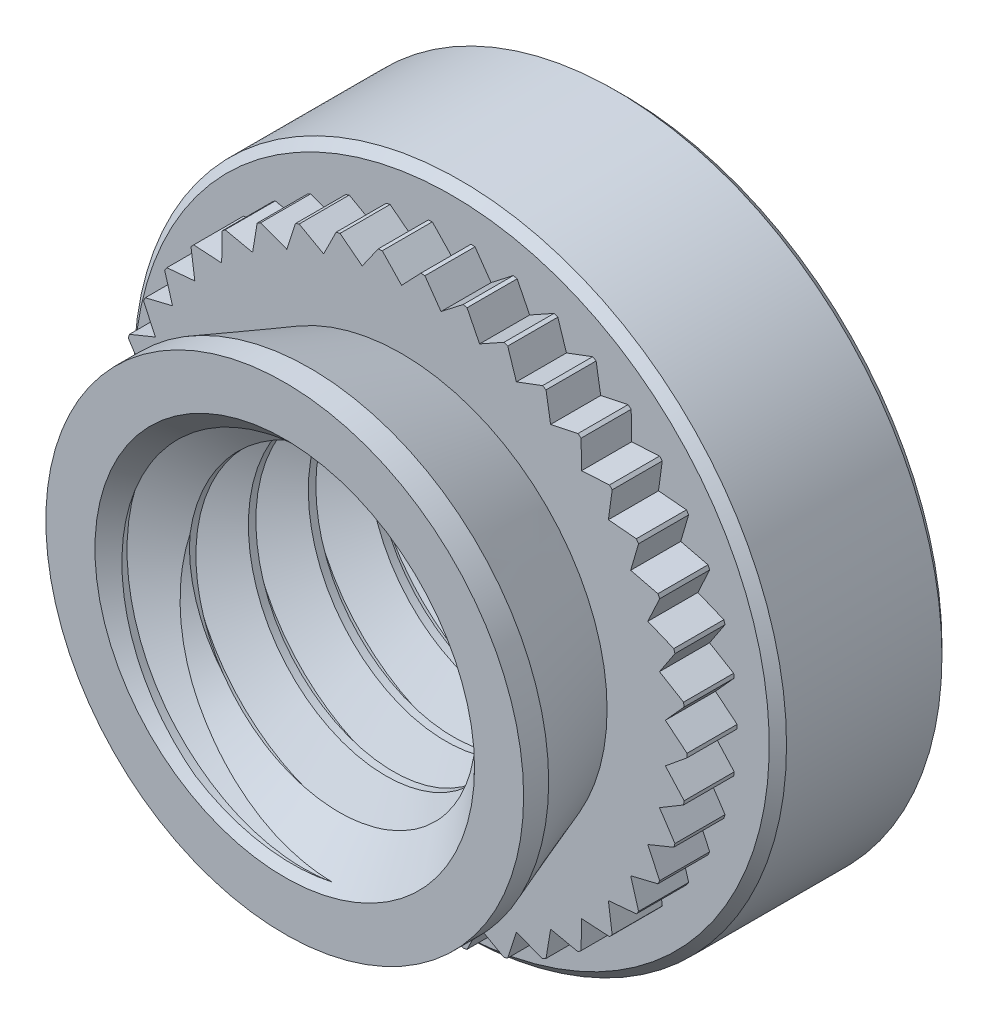
SolidWorks part; units mm, degrees
ref_plane "Front Plane" through (0, 0, 0) normal (0, 0, 1) x (1, 0, 0)
ref_plane "Top Plane" through (0, 0, 0) normal (0, 1, 0) x (1, 0, 0)
ref_plane "Right Plane" through (0, 0, 0) normal (1, 0, 0) x (0, 0, -1)
sketch "Sketch1" plane through (0, 0, 0) normal (0, 0, 1) x (1, 0, 0)
  line L0 (0, 0) -> (1.2065, -2.0897) construction
  line L1 (0, 0) -> (0, -2.413) construction
  circle A0 centre (0, 0) radius 4.318 construction
  circle A1 centre (0, 0) radius 3.1623 construction
  circle A2 centre (0, 0) radius 2.413 construction
  point P8 (1.2065, -2.0897)
  dimension "Head OD" = 8.636
  dimension "Shank OD" = 6.3246
  dimension "Thread ID" = 4.826
  dimension "D1" = 30
sketch "Sketch2" plane through (0, 0, 0) normal (1, 0, 0) x (0, 0, -1)
  line L0 (2.2479, 4.318) -> (-0.0381, 4.318) construction
  line L1 (-0.0381, 4.318) -> (-0.0381, -4.318) construction
  line L2 (-0.0381, -4.318) -> (2.2479, -4.318) construction
  line L3 (2.2479, -4.318) -> (2.2479, 4.318) construction
  line L4 (-0.0381, 3.7783) -> (-0.701, 3.7783) construction
  line L5 (-0.701, 3.7783) -> (-0.701, -3.7783) construction
  line L6 (-0.701, -3.7783) -> (-0.0381, -3.7783) construction
  line L7 (-2.2479, 3.1623) -> (-1.9164, 3.1623) construction
  line L8 (-2.2479, 3.1623) -> (-2.2479, -3.1623) construction
  line L9 (-2.2479, -3.1623) -> (-1.9164, -3.1623) construction
  line L10 (-2.2479, 0) -> (2.2479, 0) construction
  line L11 (-1.9164, -3.1623) -> (-0.701, -2.7199) construction
  line L12 (-1.9164, 3.1623) -> (-0.701, 2.7199) construction
  line L13 (0, -3.1623) -> (-2.2479, -3.1623) construction
  line L16 (2.2479, 2.413) -> (-2.2479, 2.413) construction
  line L19 (2.1983, 2.4989) -> (2.992, 2.4989) construction
  line L20 (2.992, 2.4989) -> (2.5952, 1.8115) construction
  line L21 (2.5952, 1.8115) -> (2.1983, 2.4989) construction
  line L22 (2.2231, 2.456) -> (2.9672, 2.456) construction
  line L23 (2.2479, 2.413) -> (2.9424, 2.413) construction
  line L24 (2.5456, 1.8974) -> (2.6448, 1.8974) construction
  line L25 (2.5952, 1.8974) -> (2.5952, 1.8115) construction
  line L26 (2.5952, 2.413) -> (2.5952, 2.4989) construction
  point P14 (-0.701, 0)
  point P15 (0, -4.318)
  point P16 (0, 2.413)
  point P37 (2.5952, 2.456)
  point P41 (0, 0)
  dimension "Head Height" = 2.286
  dimension "Shank Ht." = 2.2098
  dimension "D1" = 0.6629
  dimension "D3" = 7.5565
  dimension "Pitch" = 0.7937
  dimension "D7" = 0.0992
  dimension "D2" = 0.6159
  dimension "Total Height" = 4.4958
  dimension "D4" = 20
  dimension "D5" = 0.3315
sketch "Sketch3" plane through (0, 0, 0) normal (1, 0, 0) x (0, 0, -1)
  line L0 (-2.2479, 2.413) -> (2.2479, 2.413)
  line L1 (2.2479, 2.413) -> (2.2479, 4.318)
  line L2 (2.2479, 4.318) -> (-0.0381, 4.318)
  line L3 (-0.0381, 4.318) -> (-0.0381, 3.7783)
  line L4 (-0.0381, 3.7783) -> (-0.701, 3.7783)
  line L5 (-0.701, 3.7783) -> (-0.701, 2.7199)
  line L7 (-2.2479, 3.1623) -> (-2.2479, 2.413)
  line L8 (-2.2479, 0) -> (2.2479, 0) construction
  line L9 (-2.2479, 3.1623) -> (-1.9164, 3.1623)
  line L10 (-1.9164, 3.1623) -> (-0.701, 2.7199)
revolve "Revolve1" add sketch "Sketch3" angle 360 about L8
chamfer "Chamfer1" distance 0.1143 angle 45 2 edges at (4.318, 0, -2.2479) (4.318, 0, 0.0381)
sketch "Sketch5" plane through (0, 0, -2.2479) normal (0, 0, -1) x (-1, 0, 0)
  circle A0 centre (0, 0) radius 2.413 construction
  circle A1 centre (0, 0) radius 2.413
curve "Helix/Spiral1" pitch 0.7937 height 5.2895 radius 2.413 centre (0, 0, -2.2479) axis (0, 0, 1) start towards (0, 1, 0)
sketch "Sketch6" plane through (0, 0, 0) normal (1, 0, 0) x (0, 0, -1)
  line L0 (2.2231, 2.456) -> (2.9672, 2.456)
  line L1 (2.9672, 2.456) -> (2.6448, 1.8974)
  line L2 (2.6448, 1.8974) -> (2.5456, 1.8974)
  line L3 (2.5456, 1.8974) -> (2.2231, 2.456)
sweep "Sweep1" add profiles "Sketch6" path "Helix/Spiral1"
sketch "Sketch10" plane through (0, 0, 0) normal (1, 0, 0) x (0, 0, -1)
  line L1 (-2.2479, 3.1623) -> (-5.4229, 3.1623)
  line L2 (-2.2479, 3.1623) -> (-2.2479, -3.1623)
  line L3 (-2.2479, -3.1623) -> (-5.4229, -3.1623)
  line L4 (-5.4229, 3.1623) -> (-5.4229, -3.1623)
  line L5 (2.2479, 4.318) -> (5.4229, 4.318)
  line L6 (2.2479, 4.318) -> (2.2479, -4.318)
  line L7 (2.2479, -4.318) -> (5.4229, -4.318)
  line L8 (5.4229, 4.318) -> (5.4229, -4.318)
  dimension "D1" = 3.175
extrude "Cut-Extrude4" cut sketch "Sketch10" against normal through all both and the other way through all
sketch "Sketch12" plane through (0, 0, -2.2479) normal (0, 0, -1) x (-1, 0, 0)
  line L0 (0, 3.1623) -> (0, -3.1623) construction
  circle A0 centre (0, 0) radius 2.5122
  circle A1 centre (0, 0) radius 2.413 construction
  dimension "D1" = 0.0992
extrude "Cut-Extrude5" cut sketch "Sketch12" against normal up to vertex (2.2479 mm away) draft 34 up to point (0, 2.413, 0)
sketch "Sketch13" plane through (0, 0, 2.2479) normal (0, 0, 1) x (1, 0, 0)
  circle A1 centre (0, 0) radius 2.5122
  circle A2 centre (0, 0) radius 2.5122
  dimension "D1" = 0
extrude "Cut-Extrude6" cut sketch "Sketch13" against normal up to vertex (2.2479 mm away) draft 44 up to point (0, 2.413, 0)
sketch "Sketch4" plane through (0, 0, 0.0381) normal (0, 0, 1) x (1, 0, 0)
  line L2 (0, 3.5011) -> (-0.2645, 3.7783)
  line L3 (-0.2645, 3.7783) -> (0.2645, 3.7783)
  line L4 (0, 3.5011) -> (0.2645, 3.7783)
  line L5 (0, 3.1623) -> (0, -3.1623) construction
  line L7 (0, 3.7783) -> (0, 0) construction
  circle A1 centre (0, 0) radius 3.7783 construction
  dimension "D3" = 7.5565
  dimension "D1" = 0.529
  dimension "D2" = 0.2772
extrude "Cut-Extrude1" cut sketch "Sketch4" along normal up to vertex (0.6629 mm away) up to point (0, 3.7783, 0.701)
pattern_circular "CirPattern2" count 42 over 360 about axis through (0, 0, 2.2479) along (0, 0, 1) of "Cut-Extrude1"
equation "\"D1@Sketch2\"=\"Shank Ht.@Sketch2\" * .3"
equation "\"D3@Sketch2\"=\"Head OD@Sketch1\"*.875"
equation "\"D7@Sketch2\" = \"Pitch@Sketch2\" / 8"
equation "\"D1@Chamfer1\"=\"Head Height@Sketch2\"*.05"
equation "\"D1@Sketch4\"=\"D3@Sketch2\"*.07"
equation "\"D4@Helix/Spiral1\"=\"Pitch@Sketch2\""
equation "\"D3@Helix/Spiral1\"=\"Total Height@Sketch2\"+\"Pitch@Sketch2\""
equation "\"D1@Sketch10\"=\"Pitch@Sketch2\"*4"
equation "\"D1@CirPattern2\"=((\"D3@Sketch2\"*3.14)/\"D1@Sketch4\")-3"
equation "\"D2@Sketch4\"=\"D2@Sketch2\"*.45"
equation "\"D5@Sketch2\"=\"Shank Ht.@Sketch2\"*.15"
equation "\"D1@Sketch12\"=\"Pitch@Sketch2\"*.125"
